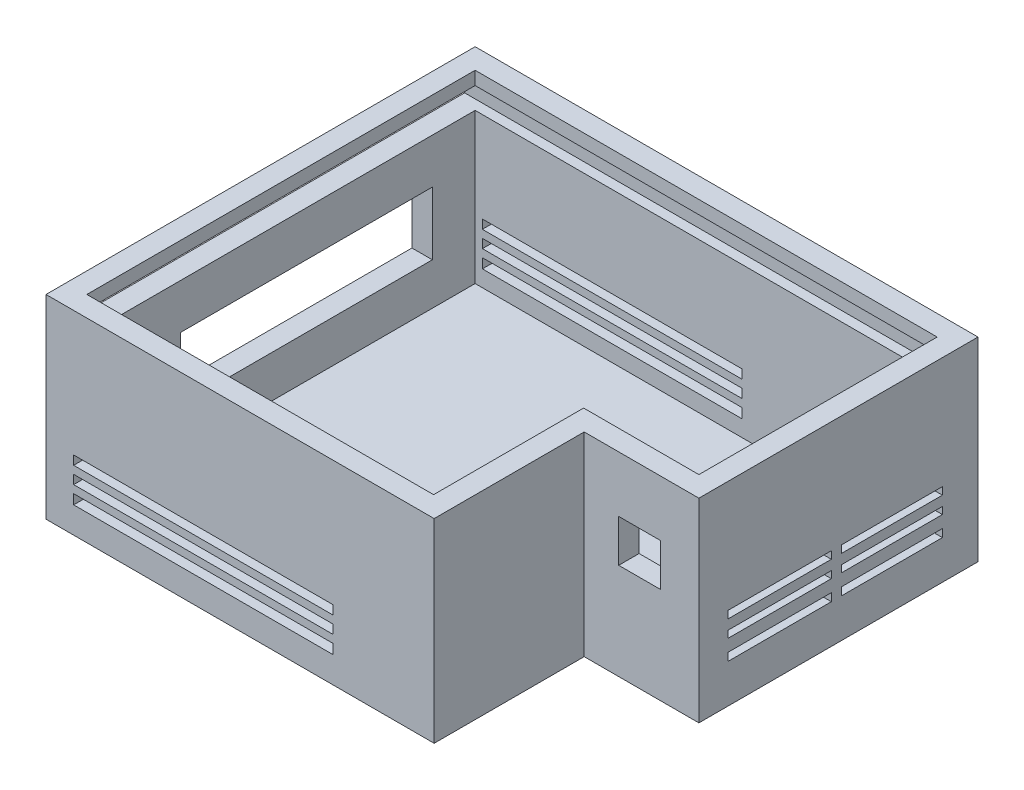
SolidWorks part; units mm, degrees
ref_plane "Front Plane" through (0, 0, 0) normal (0, 0, 1) x (1, 0, 0)
ref_plane "Top Plane" through (0, 0, 0) normal (0, 1, 0) x (1, 0, 0)
ref_plane "Right Plane" through (0, 0, 0) normal (1, 0, 0) x (0, 0, -1)
sketch "Sketch1" plane through (0, 0, 0) normal (0, 1, 0) x (1, 0, 0)
  line L0 (104.775, 0) -> (139.775, 0)
  line L1 (0, 0) -> (104.775, 0)
  line L2 (0, 0) -> (0, -117.475)
  line L3 (0, -117.475) -> (104.902, -117.475)
  line L4 (104.902, -72.0844) -> (104.902, -117.475)
  line L5 (139.775, 0) -> (139.775, -72.0844)
  line L6 (-3, -120.475) -> (104.902, -120.475)
  line L7 (104.902, -117.475) -> (104.902, -72.0844)
  line L8 (104.902, -72.0844) -> (139.775, -72.0844)
  line L9 (-3, 3) -> (-3, -120.475)
  line L10 (-3, 3) -> (104.775, 3)
  line L11 (104.775, 3) -> (142.775, 3)
  line L12 (142.775, 3) -> (142.775, -75.0844)
  line L13 (108.077, -75.0844) -> (142.775, -75.0844)
  line L14 (104.902, -72.0844) -> (107.9494, -72.0844)
  line L16 (108.077, -120.475) -> (104.902, -120.475)
  line L17 (-6.175, 6.175) -> (-6.175, -123.65)
  line L18 (104.902, -75.0844) -> (142.775, -75.0844) construction
  line L19 (-6.175, -123.65) -> (104.902, -123.65)
  line L20 (111.252, -123.65) -> (104.902, -123.65)
  line L21 (111.252, -78.2594) -> (111.252, -123.65)
  line L22 (111.252, -78.2594) -> (145.95, -78.2594)
  line L23 (145.95, 6.175) -> (145.95, -78.2594)
  line L24 (104.775, 6.175) -> (145.95, 6.175)
  line L25 (-6.175, 6.175) -> (104.775, 6.175)
  line L26 (108.077, -75.0844) -> (108.077, -120.475) construction
  dimension "D1" = 104.775
  dimension "D2" = 117.475
  dimension "D3" = 35
  dimension "D5" = 104.902
  dimension "D4" = 3
  dimension "D7" = 3.175
extrude "Boss-Extrude1" add sketch "Sketch1" along normal blind 55.88 contours L8 L4 L13 L12 L11 L10 L9 L6 L16 L7 L3 L2 L1 L0 L5 region at (49.3, 0, -4.1751)
ref_plane "Plane1" through (0, 0, 0) normal (0, 0, 1) x (1, 0, 0)
sketch "Sketch23" plane through (0, 0, 78.2594) normal (0, 0, 1) x (1, 0, 0)
  line L9 (121.6901, 38.9689) -> (134.3901, 38.9689)
  line L10 (121.6901, 38.9689) -> (121.6901, 26.1561)
  line L11 (121.6901, 26.1561) -> (134.3901, 26.1561)
  line L12 (134.3901, 38.9689) -> (134.3901, 26.1561)
  dimension "D1" = 12.8128
  dimension "D2" = 12.7
sketch "Sketch25" plane through (-6.175, 0, 0) normal (-1, 0, 0) x (0, 0, 1)
  line L4 (12.9455, 12.7) -> (89.1455, 12.7)
  line L5 (12.9455, 12.7) -> (12.9455, 31.75)
  line L6 (12.9455, 31.75) -> (89.1455, 31.75)
  line L7 (89.1455, 12.7) -> (89.1455, 31.75)
  dimension "D1" = 76.2
  dimension "D2" = 19.05
extrude "Cut-Extrude9" cut sketch "Sketch25" against normal blind 45
sketch "Sketch26" plane through (145.95, 0, 0) normal (1, 0, 0) x (0, 0, -1)
  line L0 (-35.1213, 22.0738) -> (-4.5981, 22.0738)
  line L1 (-69.4304, 11.0882) -> (-38.1973, 11.0882)
  line L2 (-69.4304, 11.0882) -> (-69.4304, 8.7152)
  line L3 (-69.4304, 8.7152) -> (-38.1973, 8.7152)
  line L4 (-4.5981, 11.0882) -> (-4.5981, 8.7152)
  line L5 (-69.4304, 14.7529) -> (-38.1973, 14.7529)
  line L6 (-69.4304, 14.7529) -> (-69.4304, 16.8722)
  line L7 (-69.4304, 16.8722) -> (-38.1973, 16.8722)
  line L8 (-4.5981, 14.7529) -> (-4.5981, 16.8722)
  line L9 (-69.4304, 19.8363) -> (-38.1973, 19.8363)
  line L10 (-69.4304, 19.8363) -> (-69.4304, 22.0738)
  line L11 (-69.4304, 22.0738) -> (-38.1973, 22.0738)
  line L12 (-4.5981, 19.8363) -> (-4.5981, 22.0738)
  line L14 (-38.1973, 22.0738) -> (-38.1973, 19.8363)
  line L16 (-35.1213, 22.0738) -> (-35.1213, 19.8363)
  line L17 (-35.1213, 19.8363) -> (-4.5981, 19.8363)
  line L18 (-35.1213, 16.8722) -> (-35.1213, 14.7529)
  line L19 (-38.1973, 16.8722) -> (-38.1973, 14.7529)
  line L20 (-35.1213, 8.7152) -> (-4.5981, 8.7152)
  line L21 (-35.1213, 11.0882) -> (-4.5981, 11.0882)
  line L22 (-35.1213, 11.0882) -> (-35.1213, 8.7152)
  line L23 (-38.1973, 11.0882) -> (-38.1973, 8.7152)
  line L24 (-35.1213, 14.7529) -> (-4.5981, 14.7529)
  line L25 (-35.1213, 16.8722) -> (-4.5981, 16.8722)
extrude "Cut-Extrude10" cut sketch "Sketch26" against normal blind 45
sketch "Sketch27" plane through (0, 0, -6.175) normal (0, 0, -1) x (-1, 0, 0)
  line L1 (-2.1913, 4.9397) -> (-80.721, 4.9397)
  line L2 (-2.1913, 4.9397) -> (-2.1913, 7.8744)
  line L3 (-2.1913, 7.8744) -> (-80.721, 7.8744)
  line L4 (-80.721, 4.9397) -> (-80.721, 7.8744)
  line L5 (-80.721, 10.2406) -> (-2.1913, 10.2406)
  line L6 (-80.721, 10.2406) -> (-80.721, 12.9398)
  line L7 (-80.721, 12.9398) -> (-2.1913, 12.9398)
  line L8 (-2.1913, 10.2406) -> (-2.1913, 12.9398)
  line L9 (-2.1913, 15.306) -> (-80.721, 15.306)
  line L10 (-2.1913, 15.306) -> (-2.1913, 18.0154)
  line L11 (-2.1913, 18.0154) -> (-80.721, 18.0154)
  line L12 (-80.721, 15.306) -> (-80.721, 18.0154)
extrude "Cut-Extrude11" cut sketch "Sketch27" against normal blind 254
extrude "Cut-Extrude12" cut sketch "Sketch23" against normal blind 50.8
sketch "Sketch31" plane through (-6.175, 0, 0) normal (-1, 0, 0) x (0, 0, 1)
  line L3 (-3, 45.3704) -> (-3, 51.8754)
  line L4 (-3, 51.8754) -> (120.5647, 51.8754)
  line L7 (120.5647, 51.8754) -> (120.5647, 45.3704)
  line L8 (120.5647, 45.3704) -> (-3, 45.3704)
extrude "Cut-Extrude13" cut sketch "Sketch31" against normal blind 113.8
sketch "Sketch34" plane through (107.625, 0, 0) normal (-1, 0, 0) x (0, 0, 1)
  line L1 (72.0844, 45.3704) -> (74.8784, 45.3704)
  line L2 (72.0844, 45.3704) -> (72.0844, 51.3704)
  line L3 (72.0844, 51.3704) -> (74.8784, 51.3704)
  line L4 (74.8784, 45.3704) -> (74.8784, 51.3704)
  line L5 (-3, 45.3704) -> (0, 45.3704)
  line L6 (-3, 45.3704) -> (-3, 51.8754)
  line L7 (-3, 51.8754) -> (0, 51.8754)
  line L8 (0, 45.3704) -> (0, 51.8754)
  dimension "D1" = 6
  dimension "D2" = 2.794
extrude "Cut-Extrude14" cut sketch "Sketch34" against normal blind 35.8
sketch "Sketch35" plane through (139.775, 0, 0) normal (-1, 0, 0) x (0, 0, 1)
  line L1 (0, 45.3704) -> (72.0844, 45.3704)
  line L2 (0, 45.3704) -> (0, 51.3704)
  line L3 (0, 51.3704) -> (72.0844, 51.3704)
  line L4 (72.0844, 45.3704) -> (72.0844, 51.3704)
extrude "Cut-Extrude15" cut sketch "Sketch35" against normal blind 2.8
sketch "Sketch36" plane through (0, 0, 0) normal (0, -1, 0) x (1, 0, 0)
  line L0 (111.252, 78.2594) -> (111.252, 123.65)
  line L1 (111.252, 123.65) -> (-6.175, 123.65)
  line L2 (-6.175, 123.65) -> (-6.175, -6.175)
  line L3 (-6.175, -6.175) -> (145.95, -6.175)
  line L4 (145.95, -6.175) -> (145.95, 78.2594)
  line L5 (145.95, 78.2594) -> (111.252, 78.2594)
extrude "Boss-Extrude2" add sketch "Sketch36" along normal blind 3
